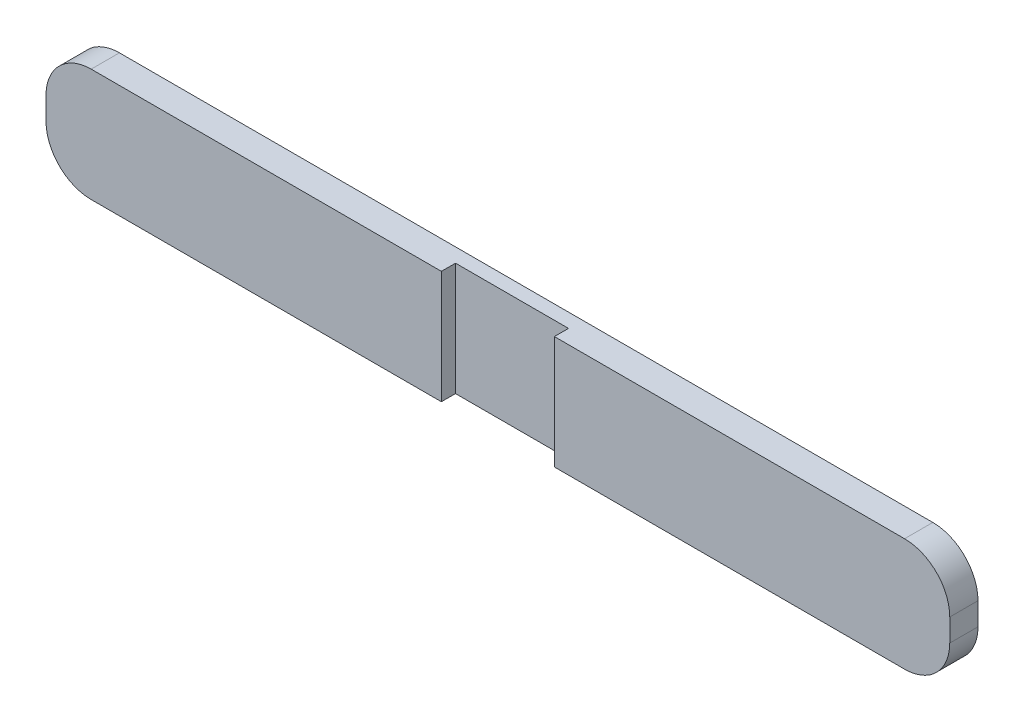
SolidWorks part; units mm, degrees
ref_plane "Front Plane" through (0, 0, 0) normal (0, 0, 1) x (1, 0, 0)
ref_plane "Top Plane" through (0, 0, 0) normal (0, 1, 0) x (1, 0, 0)
ref_plane "Right Plane" through (0, 0, 0) normal (1, 0, 0) x (0, 0, -1)
sketch "Sketch2" plane through (0, 0, 0) normal (0, 0, 1) x (1, 0, 0)
  line L1 (-17.5322, 1.7966) -> (28.1878, 1.7966)
  line L2 (-20.0722, -0.7434) -> (-20.0722, -2.0134)
  line L3 (-17.5322, -4.5534) -> (28.1878, -4.5534)
  line L4 (30.7278, -0.7434) -> (30.7278, -2.0134)
  arc A0 (30.7278, -0.7434) -> (28.1878, 1.7966) centre (28.1878, -0.7434) ccw
  arc A1 (28.1878, -4.5534) -> (30.7278, -2.0134) centre (28.1878, -2.0134) ccw
  arc A2 (-20.0722, -2.0134) -> (-17.5322, -4.5534) centre (-17.5322, -2.0134) ccw
  arc A3 (-20.0722, -0.7434) -> (-17.5322, 1.7966) centre (-17.5322, -0.7434) cw
  point P6 (30.7278, 1.7966)
  point P9 (30.7278, -4.5534)
  dimension "D3" = 2.54
  dimension "D1" = 50.8
  dimension "D2" = 6.35
extrude "Boss-Extrude1" add sketch "Sketch2" along normal blind 1.5875
sketch "Sketch3" plane through (0, 0, 1.5875) normal (0, 0, 1) x (1, 0, 0)
  line L1 (8.5028, 1.7966) -> (2.1528, 1.7966)
  line L2 (8.5028, 1.7966) -> (8.5028, -4.5534)
  line L3 (8.5028, -4.5534) -> (2.1528, -4.5534)
  line L4 (2.1528, 1.7966) -> (2.1528, -4.5534)
  line L5 (28.1878, 1.7966) -> (-17.5322, 1.7966) construction
  line L6 (-17.5322, -4.5534) -> (28.1878, -4.5534) construction
  point P6 (5.3278, 1.7966)
  point P8 (5.3278, 1.7966)
  dimension "D1" = 6.35
extrude "Cut-Extrude1" cut sketch "Sketch3" against normal blind 0.7937
